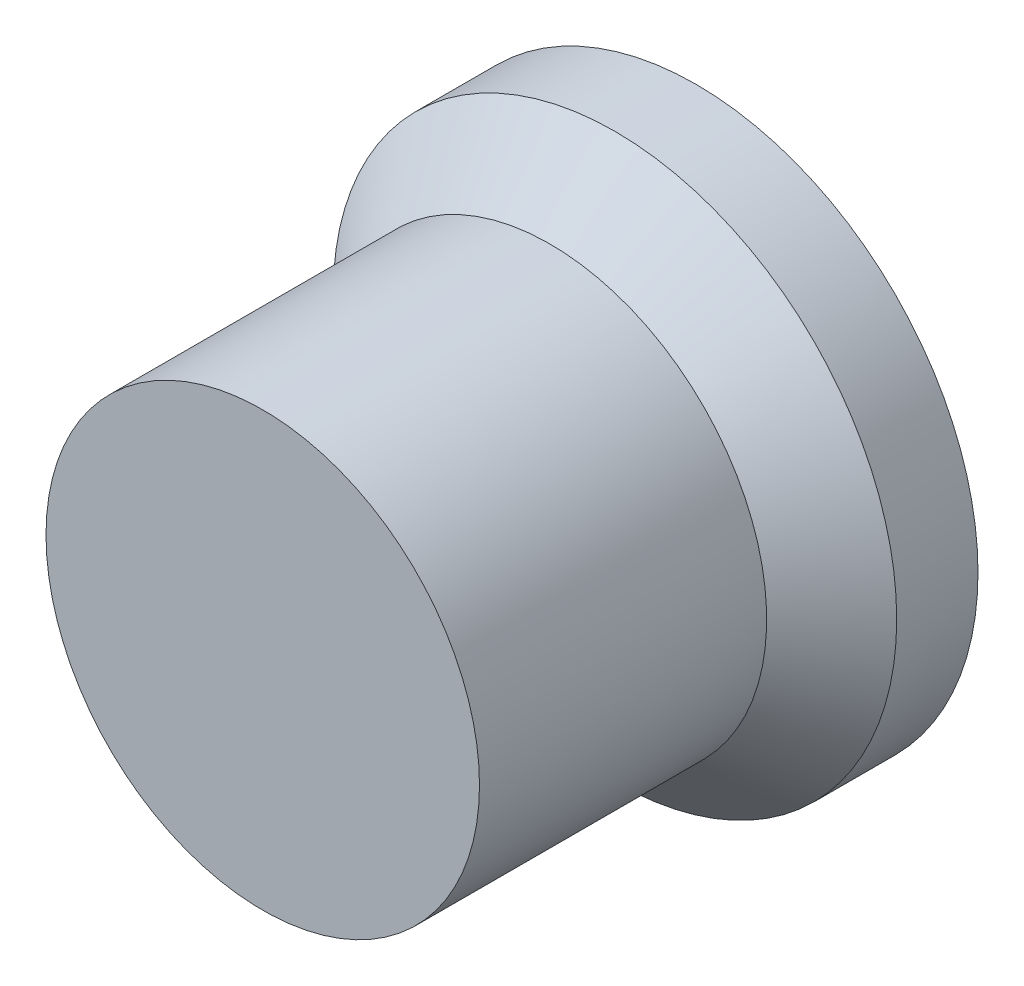
SolidWorks part; units mm, degrees
ref_plane "Front" through (0, 0, 0) normal (0, 0, 1) x (1, 0, 0)
ref_plane "Top" through (0, 0, 0) normal (0, 1, 0) x (1, 0, 0)
ref_plane "Right" through (0, 0, 0) normal (1, 0, 0) x (0, 0, -1)
sketch "Sketch1" plane through (0, 0, 0) normal (0, 0, 1) x (1, 0, 0)
  circle A0 centre (0, 0) radius 2
  dimension "D1" = 4
extrude "Boss-Extrude1" add sketch "Sketch1" along normal blind 4
sketch "Sketch2" plane through (0, 0, 0) normal (0, 0, -1) x (-1, 0, 0)
  circle A0 centre (0, 0) radius 2.6
  dimension "D1" = 5.2
extrude "Boss-Extrude2" add sketch "Sketch2" against normal blind 1.75
chamfer "Chamfer1" distance 1 angle 45 1 edges at (-2.6, 0, 1.75)
